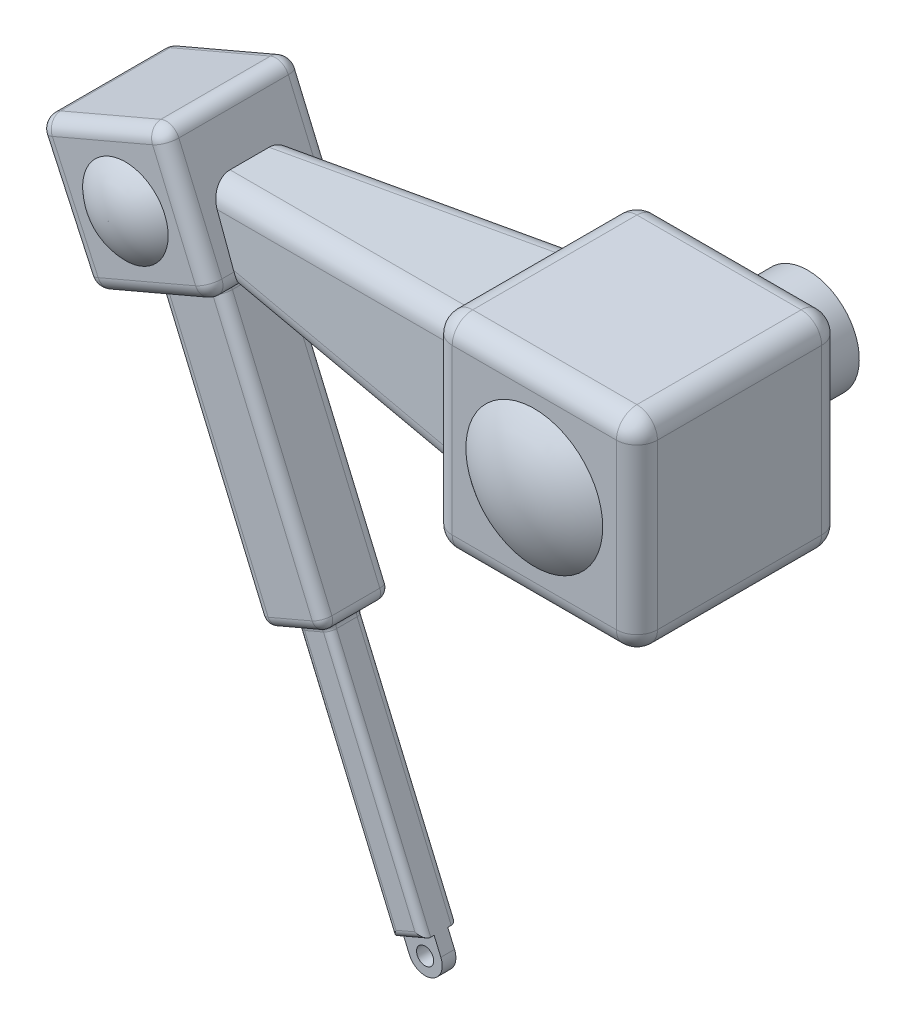
SolidWorks part; units mm, degrees
ref_plane "Front Plane" through (0, 0, 0) normal (0, 0, 1) x (1, 0, 0)
ref_plane "Top Plane" through (0, 0, 0) normal (0, 1, 0) x (1, 0, 0)
ref_plane "Right Plane" through (0, 0, 0) normal (1, 0, 0) x (0, 0, -1)
sketch "Sketch2" plane through (0, 0, 0) normal (0, 0, 1) x (1, 0, 0)
  line L0 (0, 0) -> (-1070.6415, 0) construction
  line L1 (150, -150) -> (-150, -150)
  line L2 (150, -150) -> (150, 150)
  line L3 (150, 150) -> (-150, 150)
  line L4 (-150, -150) -> (-150, 150)
  line L5 (-650, 50) -> (-150, 50)
  line L6 (-650, 50) -> (-650, -50)
  line L7 (-650, -50) -> (-150, -50)
  line L8 (-150, 50) -> (-150, -50)
  line L13 (-650, 0) -> (-300, -700) construction
  line L14 (-608.0921, -90.8392) -> (-299.5805, -812.6741) construction
  line L15 (-697.4386, -129.0258) -> (-518.7457, -52.6526)
  line L16 (-518.7457, -52.6526) -> (-597.3158, 131.1804)
  line L17 (-597.3158, 131.1804) -> (-781.2227, 52.5787)
  line L18 (-781.2227, 52.5787) -> (-697.4386, -129.0258)
  line L20 (-404.912, -439.0028) -> (-496.8655, -478.3036)
  line L21 (-496.8655, -478.3036) -> (-654.0689, -110.4897)
  line L22 (-654.0689, -110.4897) -> (-562.1154, -71.1888)
  line L23 (-562.1154, -71.1888) -> (-404.912, -439.0028)
  line L24 (-276.5921, -802.8489) -> (-322.5689, -822.4993)
  line L25 (-322.5689, -822.4993) -> (-473.8771, -468.4784)
  line L26 (-473.8771, -468.4784) -> (-427.9004, -448.828)
  line L27 (-427.9004, -448.828) -> (-276.5921, -802.8489)
  line L29 (-286.4173, -779.8605) -> (-332.3941, -799.5109)
  circle A0 centre (-299.5805, -812.6741) radius 25
  circle A1 centre (-299.5805, -812.6741) radius 12.5
  point P17 (-650, 0)
  dimension "D22" = 50
  dimension "D24" = 25
  dimension "D1" = 300
  dimension "D2" = 150
  dimension "D3" = 300
  dimension "D4" = 150
  dimension "D5" = 0
  dimension "D6" = 500
  dimension "D7" = 100
  dimension "D8" = 50
  dimension "D9" = 100
  dimension "D10" = 200
  dimension "D11" = 100
  dimension "D12" = 200
  dimension "D13" = 700
  dimension "D14" = 0
  dimension "D15" = 350
  dimension "D16" = 50
  dimension "D17" = 0
  dimension "D18" = 400
  dimension "D19" = 25
  dimension "D20" = 0
  dimension "D21" = 385
  dimension "D23" = 50
  dimension "D25" = 25
  dimension "D26" = 100
extrude "Boss-Extrude3" add sketch "Sketch2" along normal blind 50 contours L16 L7 L4 L5 | L7 L16 L5 L6 region at (-345.8192, 0.9103, 0) region at (-594.9248, -3.2751, 0)
extrude "Boss-Extrude4" add sketch "Sketch2<5>" against normal blind 50 contours L16 L7 L4 L5 | L7 L16 L5 L6 region at (-345.8192, 0.9103, 0) region at (-594.9248, -3.2751, 0)
sketch "Sketch2<5>" plane through (0, 0, 0) normal (0, 0, 1) x (1, 0, 0) same geometry as "Sketch2"
draft "Draft2" type of draft neutral plane draft angle 5.711 faces to draft 4 face at (-400, 50, 0) face at (-400, 0, -50) face at (-400, -50, 0) face at (-400, 0, 50) neutral plane through (-650, 0, 50) neutral plane normal (-1, 0, 0) parameters "D1"=5.711
extrude "Boss-Extrude5" add sketch "Sketch2<6>" along normal blind 150 contours L4 L1 L2 L3 region at (0, 0, 0)
sketch "Sketch2<6>" plane through (0, 0, 0) normal (0, 0, 1) x (1, 0, 0) same geometry as "Sketch2"
extrude "Boss-Extrude6" add sketch "Sketch2<7>" against normal blind 150 contours L4 L1 L2 L3 region at (0, 0, 0)
sketch "Sketch2<7>" plane through (0, 0, 0) normal (0, 0, 1) x (1, 0, 0) same geometry as "Sketch2"
extrude "Boss-Extrude7" add sketch "Sketch2<8>" along normal blind 100 contours L17 L18 L15 L16 L7 L6 L5 | L7 L16 L5 L6 region at (-669.4314, 2.571, 0) region at (-594.9248, -3.2751, 0)
sketch "Sketch2<8>" plane through (0, 0, 0) normal (0, 0, 1) x (1, 0, 0) same geometry as "Sketch2"
extrude "Boss-Extrude8" add sketch "Sketch2<9>" against normal blind 100 contours L17 L18 L15 L16 L7 L6 L5 | L7 L16 L5 L6 region at (-669.4314, 2.571, 0) region at (-594.9248, -3.2751, 0)
sketch "Sketch2<9>" plane through (0, 0, 0) normal (0, 0, 1) x (1, 0, 0) same geometry as "Sketch2"
sketch3d "3DSketch1"
  point P0 (-13.4954, -22.5537, -150)
ref_plane "Plane1" through (0, 0, -150) normal (0, 0, -1) x (-1, 0, 0)
sketch "Sketch4" plane through (0, 0, -150) normal (0, 0, -1) x (-1, 0, 0)
  line L0 (150, -150) -> (150, 150) construction
  circle A0 centre (0, 0) radius 75
  dimension "D1" = 150
  dimension "D2" = 150
extrude "Boss-Extrude9" add sketch "Sketch4" along normal blind 100
sketch3d "3DSketch2"
  point P0 (-657.4791, -111.9472, 21.0827)
extrude "Boss-Extrude12" add sketch "Sketch2<10>" along normal blind 50 contours L23 L15 L21 L20 region at (-529.4904, -274.7462, 0)
sketch "Sketch2<10>" plane through (0, 0, 0) normal (0, 0, 1) x (1, 0, 0) same geometry as "Sketch2"
extrude "Boss-Extrude13" add sketch "Sketch2<11>" against normal blind 50 contours L23 L15 L21 L20 region at (-529.4904, -274.7462, 0)
sketch "Sketch2<11>" plane through (0, 0, 0) normal (0, 0, 1) x (1, 0, 0) same geometry as "Sketch2"
extrude "Boss-Extrude16" add sketch "Sketch2<16>" along normal blind 25 contours L29 L27 L20 L25 region at (-380.1472, -624.1695, 0)
sketch "Sketch2<16>" plane through (0, 0, 0) normal (0, 0, 1) x (1, 0, 0) same geometry as "Sketch2"
extrude "Boss-Extrude17" add sketch "Sketch2<17>" against normal blind 25 contours L29 L27 L20 L25 region at (-380.1472, -624.1695, 0)
sketch "Sketch2<17>" plane through (0, 0, 0) normal (0, 0, 1) x (1, 0, 0) same geometry as "Sketch2"
extrude "Boss-Extrude18" add sketch "Sketch2<18>" along normal blind 10 contours A1 L24 A0 | A0 L29 L25 | A0 L27 L29 | A1 L24 A0 region at (-289.3576, -787.19, 0) region at (-325.0646, -802.4512, 0) region at (-275.6694, -807.7785, 0) region at (-282.5722, -804.76, 0)
sketch "Sketch2<18>" plane through (0, 0, 0) normal (0, 0, 1) x (1, 0, 0) same geometry as "Sketch2"
extrude "Boss-Extrude19" add sketch "Sketch2<20>" against normal blind 10 contours A0 L29 L25 | A1 L24 A0 | A1 L24 A0 | A0 L27 L29 region at (-289.3576, -787.19, 0) region at (-325.0646, -802.4512, 0) region at (-275.6694, -807.7785, 0) region at (-282.5722, -804.76, 0)
sketch "Sketch2<20>" plane through (0, 0, 0) normal (0, 0, 1) x (1, 0, 0) same geometry as "Sketch2"
fillet "Fillet2" radius 10 10 edges at (-357.1589, -614.3443, -25) (-403.1356, -633.9947, -25) (-309.4057, -789.6857, -25) (-403.1356, -633.9947, 25) (-357.1589, -614.3443, 25) (-309.4057, -789.6857, 25) (-473.8771, -468.4784, 0) (-427.9004, -448.828, 0) (-450.8887, -458.6532, -25) (-450.8887, -458.6532, 25)
fillet "Fillet4" radius 15 12 edges at (-608.0921, -90.8392, -50) (-450.8887, -458.6532, -50) (-562.1154, -71.1888, 0) (-483.5137, -255.0958, -50) (-404.912, -439.0028, 0) (-496.8655, -478.3036, 0) (-575.4672, -294.3966, -50) (-654.0689, -110.4897, 0) (-450.8887, -458.6532, 50) (-575.4672, -294.3966, 50) (-608.0921, -90.8392, 50) (-483.5137, -255.0958, 50)
fillet "Fillet5" radius 20 13 edges at (-608.0921, -90.8392, 100) (-689.2692, 91.8796, 100) (-558.0307, 39.2639, 100) (-739.3306, -38.2236, 100) (-697.4386, -129.0258, 0) (-781.2227, 52.5787, 0) (-689.2692, 91.8796, -100) (-739.3306, -38.2236, -100) (-608.0921, -90.8392, -100) (-558.0307, 39.2639, -100) (-518.7457, -52.6526, -81.5627) (-518.7457, -52.6526, 81.5627) (-597.3158, 131.1804, 0)
fillet "Fillet6" radius 30 4 edges at (-358.1004, 79.19, 79.19) (-344.3015, -80.5698, 80.5698) (-344.3015, -80.5698, -80.5698) (-358.1004, 79.19, -79.19)
fillet "Fillet7" radius 30 12 edges at (-150, 0, 150) (0, -150, 150) (0, -150, -150) (-150, -150, 0) (150, 0, 150) (150, 0, -150) (150, -150, 0) (0, 150, 150) (-150, 150, 0) (0, 150, -150) (150, 150, 0) (-150, 0, -150)
sketch3d "3DSketch5"
  point P0 (-700.8477, 30.8135, 100)
ref_plane "Plane5" through (0, 0, 100) normal (0, 0, 1) x (1, 0, 0)
sketch "Sketch5" plane through (0, 0, 100) normal (0, 0, 1) x (1, 0, 0)
  line L3 (-551.3997, -224.1959) -> (-745.2966, 229.4713) construction
  line L6 (-360.0944, 123.8617) -> (-840.1382, -81.3086) construction
  circle A1 centre (-647.6343, 0.9674) radius 62.5
  dimension "D1" = 125
extrude "Boss-Extrude20" add sketch "Sketch5" along normal blind 25
fillet "Fillet8" radius 90 1 edges at (-585.1343, 0.9674, 125)
sketch3d "3DSketch6"
  point P0 (-11.3942, -58.5649, 150)
ref_plane "Plane6" through (0, 0, 150) normal (0, 0, 1) x (1, 0, 0)
sketch "Sketch6" plane through (0, 0, 150) normal (0, 0, 1) x (1, 0, 0)
  circle A0 centre (0, 0) radius 100
  dimension "D1" = 200
extrude "Boss-Extrude21" add sketch "Sketch6" along normal blind 35
fillet "Fillet9" radius 160 1 edges at (100, 0, 185)
